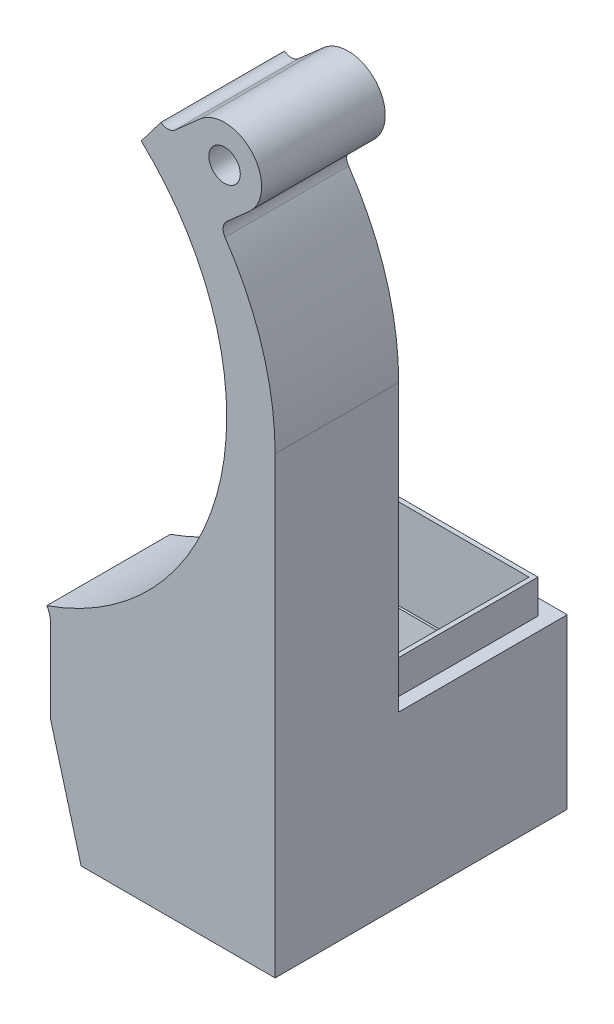
SolidWorks part; units mm, degrees
ref_plane "Front Plane" through (0, 0, 0) normal (0, 0, 1) x (1, 0, 0)
ref_plane "Top Plane" through (0, 0, 0) normal (0, 1, 0) x (1, 0, 0)
ref_plane "Right Plane" through (0, 0, 0) normal (1, 0, 0) x (0, 0, -1)
sketch "Sketch1" plane through (0, 0, 0) normal (0, 0, 1) x (1, 0, 0)
  line L0 (25.1853, 17.5272) -> (23.2069, 15.7789)
  line L1 (20.8147, 22.4728) -> (18.5989, 20.5146)
  line L2 (17.3331, 20.4667) -> (15.5862, 18.1594)
  line L3 (7.5, -25.4) -> (7.5, -22.9558)
  line L4 (7.5, -25.4) -> (27.5, -25.4)
  line L5 (27.5, -25.4) -> (27.5, 0)
  circle A0 centre (23, 20) radius 1.4
  arc A1 (25.1853, 17.5272) -> (20.8147, 22.4728) centre (23, 20) ccw
  arc A2 (23.2069, 15.7789) -> (23.0428, 14.4662) centre (23.8691, 15.0296) ccw
  arc A3 (18.5989, 20.5146) -> (17.3331, 20.4667) centre (17.9367, 21.2639) cw
  arc A4 (15.5862, 18.1594) -> (7.1741, -21.8616) centre (-0.6849, 0.6849) cw
  arc A6 (21.1912, 0.5) -> (15.788, 15.0809) centre (-0.6849, 0.6849) ccw construction
  arc A7 (7.5, -22.9558) -> (4.899, -21.0483) centre (5.5, -22.9558) ccw
  arc A8 (7.5, -22.9558) -> (4.899, -21.0483) centre (5.5, -22.9558) ccw construction
  arc A9 (27.5, 0) -> (23.0428, 14.4662) centre (1.85, 0.0168) ccw
  dimension "D1" = 2
  dimension "D2" = 2.8
extrude "Boss-Extrude1" add sketch "Sketch1" along normal blind 11 contours L5 A9 A2 L0 A1 L1 A3 L2 A4 A7 L3 L4 A0 region at (23.8466, 17.0485, 0)
sketch "Sketch2" plane through (0, -25.4, 0) normal (0, -1, 0) x (1, 0, 0)
  line L0 (8.5, -13.8) -> (8.5, -8) construction
  line L5 (7.5, -15) -> (27.5, -15)
  line L6 (7.5, -15) -> (7.5, 11)
  line L7 (7.5, 11) -> (27.5, 11)
  line L8 (27.5, -15) -> (27.5, 11)
  line L9 (8.5, -13.8) -> (26.5, -13.8)
  line L10 (8.5, -13.8) -> (8.5, -0.9)
  line L11 (8.5, -0.9) -> (26.5, -0.9)
  line L12 (26.5, -13.8) -> (26.5, -0.9)
  line L13 (26.5, -13.8) -> (8.5, -13.8) construction
  line L14 (26.5, -0.9) -> (8.5, -0.9) construction
  line L15 (26.5, -0.9) -> (26.5, -8) construction
  line L17 (25.9, -13.2) -> (9.1, -13.2)
  line L18 (25.9, -13.2) -> (25.9, -1.5)
  line L19 (25.9, -1.5) -> (9.1, -1.5)
  line L20 (9.1, -13.2) -> (9.1, -1.5)
  line M13 (7.5, 0) -> (27.5, 0)
  line M14 (27.5, 0) -> (27.5, 11)
  line M15 (27.5, 11) -> (7.5, 11)
  line M16 (7.5, 11) -> (7.5, 0)
  dimension "D1" = 0
  dimension "D2" = 0
  dimension "D3" = 0
  dimension "D4" = 0
  dimension "D5" = 0.6
  dimension "D6" = 0.6
  dimension "D7" = 0.6
  dimension "D8" = 0.6
extrude "Boss-Extrude2" add sketch "Sketch2" against normal blind 3 separate body contours L9 L12 L11 L10 L17 L20 L19 L18 region at (8.7215, -25.4, -7.35)
extrude "Boss-Extrude3" add sketch "Sketch2<3>" along normal blind 5 contours M16 M13 M14 M15 | L5 L8 L6 L12 L9 L10 L11 M13 | L9 L12 L11 L10 L17 L20 L19 L18 region at (7.75, -25.4, -7.5) region at (17.5, -25.4, 5.5) region at (8.7215, -25.4, -7.35)
sketch "Sketch2<3>" plane through (0, -25.4, 0) normal (0, -1, 0) x (1, 0, 0) same geometry as "Sketch2"
sketch "Sketch4" plane through (0, 0, -15) normal (0, 0, -1) x (-1, 0, 0)
  line L0 (-7.5, -30.4) -> (-18.4267, -70.4)
  line L1 (-18.4267, -70.4) -> (-20.5, -70.4)
  line L2 (-20.5, -70.4) -> (-9.5733, -30.4)
  line L3 (-7.5, -30.4) -> (-27.5, -30.4) construction
  line L4 (-9.5733, -30.4) -> (-7.5, -30.4)
  line L5 (-27.5, -30.4) -> (-27.5, -70.4)
  line L6 (-27.5, -70.4) -> (-25.5, -70.4)
  line L7 (-25.5, -70.4) -> (-25.5, -30.4)
  line L8 (-25.5, -30.4) -> (-27.5, -30.4)
  line L10 (-9.5733, -30.4) -> (-25.5, -30.4)
  line L11 (-20.5, -70.4) -> (-25.5, -70.4)
  line M3 (-27.5, -30.4) -> (-7.5, -30.4)
  dimension "D1" = 2
  dimension "D2" = 2
  dimension "D3" = 5
  dimension "D4" = 40
  dimension "D5" = 40
extrude "Boss-Extrude4" add sketch "Sketch4" against normal blind 2 contours L11 L2 L7 M3 | L6 L7 L5 M3 | L2 L1 L0 M3 region at (14, -50.4, -15) region at (19.7929, -46.9191, -15) region at (26.5, -50.4, -15)
extrude "Boss-Extrude6" add sketch "Sketch4<3>" against normal blind 22 from surface separate body contours L2 L1 L0 M3 | L6 L7 L5 M3 region at (14, -50.4, -15) region at (26.5, -50.4, -15) starting at face at (19.3211, -43.7333, -13)
sketch "Sketch4<3>" plane through (0, 0, -15) normal (0, 0, -1) x (-1, 0, 0) same geometry as "Sketch4"
extrude "Boss-Extrude7" add sketch "Sketch4<4>" against normal up to surface (26 mm away) from surface contours L11 L2 L7 M3 | L2 L1 L0 M3 | L6 L7 L5 M3 region at (14, -50.4, -15) region at (19.7929, -46.9191, -15) region at (26.5, -50.4, -15) up to face at (24.4, 20, 11) starting at face at (26.5, -50.4, 9)
sketch "Sketch4<4>" plane through (0, 0, -15) normal (0, 0, -1) x (-1, 0, 0) same geometry as "Sketch4"
sketch "Sketch8" plane through (25.5, 0, 0) normal (-1, 0, 0) x (0, 0, 1)
  line L0 (-13, -70.4) -> (-6, -70.4)
  line L1 (9, -70.4) -> (-13, -70.4) construction
  line L2 (-6, -70.4) -> (-13, -30.4)
  line L3 (-13, -30.4) -> (-13, -70.4)
  dimension "D1" = 40
  dimension "D2" = 7
extrude "Boss-Extrude8" add sketch "Sketch8" along normal up to surface (5 mm away) up to face at (13.944, -46.4, -1.9)
extrude "Cut-Extrude-Thin6" cut sketch "Sketch2<5>" against normal blind 10 from surface thin contours L10 L11 L12 L9 starting at face at (17.5, -25.4, -7.35) thin type one direction reverse wall 0.2
sketch "Sketch2<5>" plane through (0, -25.4, 0) normal (0, -1, 0) x (1, 0, 0) same geometry as "Sketch2"
sketch "Sketch11" plane through (0, 0, -15) normal (0, 0, -1) x (-1, 0, 0)
  line L0 (-18.4267, -70.4) -> (-27.5, -70.4) construction
  line L1 (0, -40.4) -> (-50.1346, -40.4)
  line L2 (0, -40.4) -> (0, -70.4)
  line L3 (0, -70.4) -> (-50.1346, -70.4)
  line L4 (-50.1346, -40.4) -> (-50.1346, -70.4)
  dimension "D1" = 0
  dimension "D2" = 30
extrude "Cut-Extrude6" cut sketch "Sketch11" against normal through all
ref_plane "Plane1" through (0, 0, 30) normal (0, 0, 1) x (1, 0, 0)
